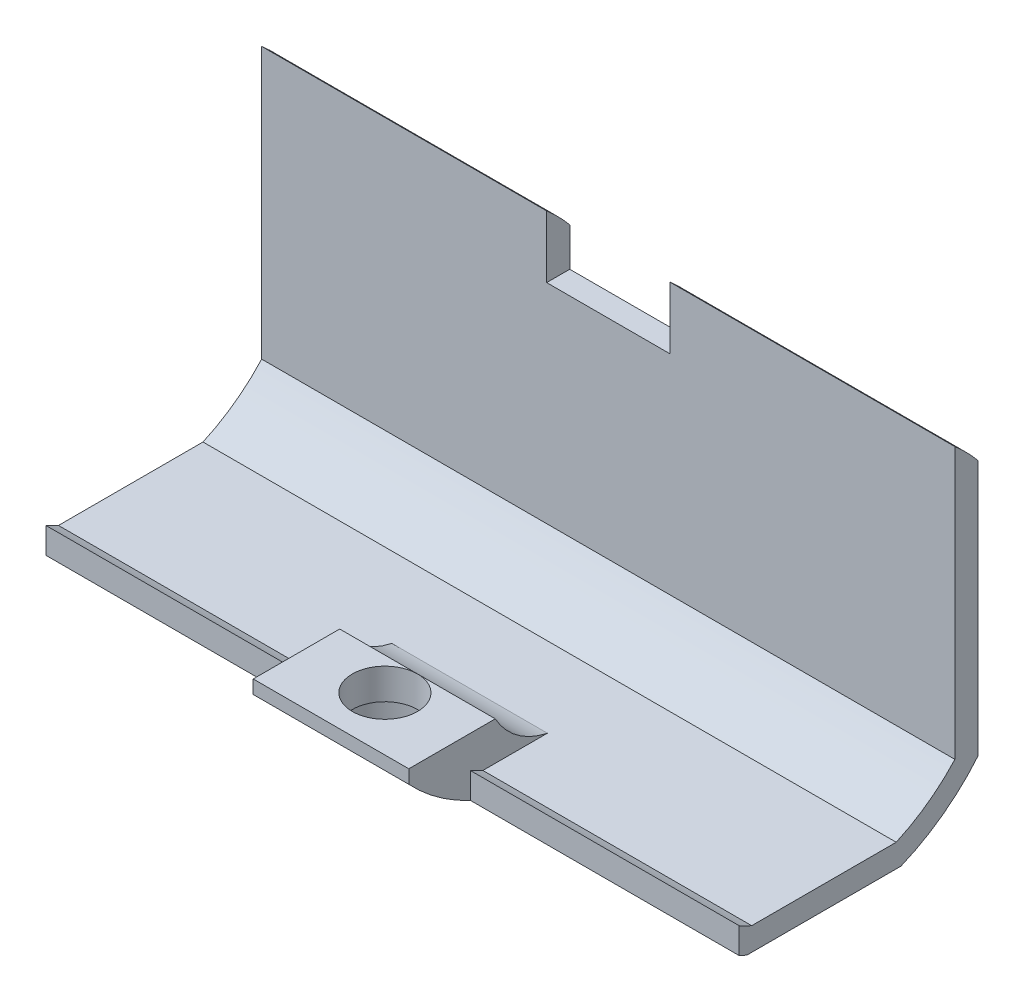
SolidWorks part; units mm, degrees
ref_plane "Plano frontal" through (0, 0, 0) normal (0, 0, 1) x (1, 0, 0)
ref_plane "Plano superior" through (0, 0, 0) normal (0, 1, 0) x (1, 0, 0)
ref_plane "Plano direito" through (0, 0, 0) normal (1, 0, 0) x (0, 0, -1)
sketch "Esboço2" plane through (0, 0, 0) normal (0, 0, 1) x (1, 0, 0)
  line L0 (0, 47.2571) -> (8.5, 47.2571)
  line L1 (0, 47.2571) -> (-8.5, 47.2571)
  line L2 (0, 23.9177) -> (8.5, 23.9177)
  line L3 (0, 23.9177) -> (-8.5, 23.9177)
  line L4 (0, 8.4) -> (0, 75) construction
  line L5 (0, 56.3545) -> (-16, 56.3545) construction
  line L6 (0, 56.3545) -> (16, 56.3545) construction
  line L7 (8.5, 47.2571) -> (8.5, 23.9177)
  line L8 (-8.5, 47.2571) -> (-8.5, 23.9177)
  line L20 (19.3117, 92) -> (-19.3117, 92)
  line L21 (-19.3117, 92) -> (-36.5, 70)
  line L22 (-36.5, 70) -> (-36.5, 0)
  line L23 (-36.5, 0) -> (-22.5, 0)
  line L24 (-22.5, 0) -> (-22.5, 8.4)
  line L25 (-22.5, 8.4) -> (22.5, 8.4)
  line L26 (22.5, 8.4) -> (22.5, 0)
  line L27 (22.5, 0) -> (36.5, 0)
  line L28 (36.5, 0) -> (36.5, 70)
  line L29 (36.5, 70) -> (19.3117, 92)
  circle A8 centre (29.2, 62) radius 2
  circle A9 centre (29.2, 49) radius 2
  circle A10 centre (29.2, 36) radius 2
  circle A11 centre (29.2, 23) radius 2
  circle A12 centre (-29.2, 23) radius 2
  circle A13 centre (0, 75) radius 2
  circle A14 centre (-7, 83.3) radius 2
  circle A15 centre (7, 83.3) radius 2
  circle A16 centre (-29.2, 36) radius 2
  circle A17 centre (-29.2, 49) radius 2
  circle A18 centre (-29.2, 62) radius 2
  circle A20 centre (-29.2, 10) radius 2
  circle A21 centre (29.2, 10) radius 2
  circle A26 centre (-16, 56.3545) radius 2.0867
  circle A27 centre (16, 56.3545) radius 2.0867
  point P31 (0, 23.9177)
  point P33 (0, 47.2571)
sketch "Model" plane through (0, 0, 0) normal (0, 0, 1) x (1, 0, 0)
  line L0 (-13.5, 51.7) -> (0, 51.7) construction
  line L1 (-22.5, 41.7) -> (0, 41.7) construction
  line L2 (0, 50.7729) -> (-23, 50.7729) construction
  line L3 (-22.5, 61.7) -> (-22.5, 41.7) construction
  line L4 (-22.5, 61.7) -> (0, 61.7) construction
  line L5 (-22.5, 61.7) -> (-21, 61.7) construction
  line L6 (-21, 61.7) -> (-21, 43.2) construction
  line L7 (0, 61.7) -> (0, 41.7) construction
  line L8 (0, 61.7) -> (0, 59.2) construction
  line L9 (0, 44.2) -> (0, 59.2)
  line L10 (-23, 63.7) -> (-23, 39.7)
  line L11 (-5.2, 59.2) -> (-0.8, 59.2) construction
  line L12 (-23, 63.7) -> (-5.55, 63.7)
  line L13 (0, 41.7) -> (0, 42.7) construction
  line L14 (-5.55, 63.7) -> (-5.55, 59.2)
  line L15 (0, 42.7) -> (-3.75, 42.7) construction
  line L16 (-3, 57) -> (-3, 61.4) construction
  line L17 (0, 59.2) -> (-5.55, 59.2)
  line L18 (-3, 61.4) -> (0, 61.4) construction
  line L19 (-3, 57) -> (0, 57) construction
  line L20 (-3.75, 41.7) -> (-3.75, 43.7) construction
  line L21 (0, 51.7) -> (-23, 51.7) construction
  line L22 (-3.75, 43.7) -> (0, 43.7) construction
  line L23 (-23, 39.7) -> (-5.55, 39.7)
  line L24 (-3.75, 41.7) -> (-3.75, 34.7) construction
  line L25 (-3.75, 34.7) -> (0, 34.7) construction
  line L26 (-5.55, 39.7) -> (-5.55, 44.2)
  line L27 (0, 44.2) -> (-5.55, 44.2)
  line L34 (-9.5, 39.7) -> (-17.5, 39.7) construction
  line L35 (-17.5, 39.7) -> (-25.5, 47.7) construction
  line L36 (-25.5, 47.7) -> (-25.5, 55.7) construction
  line L37 (-25.5, 55.7) -> (-17.5, 63.7) construction
  line L38 (-17.5, 63.7) -> (-9.5, 63.7) construction
  line L39 (-9.5, 63.7) -> (-5.55, 59.2) construction
  line L40 (-3, 46.75) -> (0, 46.75) construction
  line L41 (-3, 56.65) -> (0, 56.65) construction
  line L42 (-5.55, 44.2) -> (-5.55, 41.2) construction
  line L44 (-2.5, 36.75) -> (-5.55, 41.2) construction
  line L45 (-2.5, 36.75) -> (-2.5, 31.7) construction
  line L48 (-9.5, 31.7) -> (-9.5, 39.7) construction
  line L50 (-2.5, 31.7) -> (-2.5, 29.7) construction
  line L51 (-2.5, 29.7) -> (-9.5, 29.7) construction
  line L52 (-9.5, 29.7) -> (-9.5, 31.7) construction
  line L56 (-36.5, 50.7729) -> (-23.5, 50.7729) construction
  line L57 (-36.5, 70) -> (-36.5, 0) construction
  line L58 (0, 8.4) -> (0, 75) construction
  circle A0 centre (-13.5, 51.7) radius 8.35
  circle A2 centre (-21, 43.2) radius 1 construction
  circle A4 centre (-3, 59.2) radius 2.2 construction
  circle A7 centre (-13.5, 51.7) radius 8 construction
  arc A10 (-5.55, 59.2) -> (-3, 56.65) centre (-3, 59.2) ccw construction
  arc A11 (-3, 46.75) -> (-5.55, 44.2) centre (-3, 44.2) ccw construction
extrude "Ressalto-extrusão2" add sketch "Model" along normal blind 4
sketch "Esboço5" plane through (0, 0, 0) normal (0, 0, -1) x (-1, 0, 0)
  line L1 (23, 63.7) -> (25, 63.7)
  line L2 (23, 63.7) -> (23, 39.7)
  line L3 (23, 39.7) -> (25, 39.7)
  line L4 (25, 63.7) -> (25, 39.7)
extrude "Ressalto-extrusão3" add sketch "Esboço5" against normal blind 20
sketch "Esboço6" plane through (-25, 0, 0) normal (-1, 0, 0) x (0, 0, 1)
  line L0 (0, 51.7) -> (20, 51.7) construction
  line L1 (0, 39.7) -> (0, 63.7) construction
  line L2 (20, 39.7) -> (20, 63.7) construction
  line L3 (20, 51.7) -> (10, 63.7) construction
  line L4 (20, 63.7) -> (0, 63.7) construction
  line L5 (10, 63.7) -> (10, 39.7) construction
  line L6 (20, 39.7) -> (0, 39.7) construction
  circle A0 centre (10, 51.7) radius 13
extrude "Corte-extrusão1" cut sketch "Esboço6" against normal through all flip side to cut
sketch "Esboço8" plane through (-25, 0, 0) normal (-1, 0, 0) x (0, 0, 1)
  line L0 (10, 63.7) -> (10, 39.7) construction
  line L1 (15, 63.7) -> (5, 63.7) construction
  line L2 (15, 39.7) -> (5, 39.7) construction
  line L3 (10, 39.7) -> (0, 51.7) construction
  line L4 (0, 43.3934) -> (0, 60.0066) construction
  line L5 (0, 51.7) -> (20, 51.7) construction
  line L6 (20, 43.3934) -> (20, 60.0066) construction
  line L7 (10, 51.7) -> (7.885, 51.7) construction
  line L8 (10, 51.7) -> (8.5045, 53.1955) construction
  line L9 (10, 51.7) -> (10, 53.815) construction
  line L10 (10, 51.7) -> (11.4955, 53.1955) construction
  line L11 (10, 51.7) -> (12.115, 51.7) construction
  line L12 (10, 51.7) -> (11.4955, 50.2045) construction
  line L13 (10, 51.7) -> (10, 49.585) construction
  line L14 (10, 51.7) -> (8.5045, 50.2045) construction
  line L15 (7.885, 51.7) -> (10, 49.585)
  line L16 (10, 49.585) -> (12.115, 51.7)
  line L17 (12.115, 51.7) -> (10, 53.815)
  line L18 (10, 53.815) -> (7.885, 51.7)
  circle A0 centre (10, 51.7) radius 2.115 construction
  point P24 (10, 51.7)
  dimension "D1" = 8
extrude "Corte-extrusão2" cut sketch "Esboço8" against normal through all
mirror "Espelhar1" about plane through (0, 44.2, 4) normal (-1, 0, 0) of bodies 105
sketch "Esboço9" plane through (0, 0, 4) normal (0, 0, 1) x (1, 0, 0)
  line L0 (0, 59.2) -> (4, 59.2)
  line L1 (5.55, 59.2) -> (-5.55, 59.2) construction
  line L2 (4, 59.2) -> (4, 44.2)
  line L3 (-5.55, 44.2) -> (5.55, 44.2) construction
  line L4 (4, 44.2) -> (-4, 44.2)
  line L5 (-4, 44.2) -> (-4, 59.2)
  line L6 (-4, 59.2) -> (0, 59.2)
extrude "Ressalto-extrusão4" add sketch "Esboço9" along normal blind 4
sketch "Esboço10" plane through (0, 59.2, 0) normal (0, 1, 0) x (1, 0, 0)
  line L0 (0, 0) -> (0, -8) construction
  line L1 (4, -8) -> (-4, -8) construction
  line L2 (0, -4) -> (2.115, -4) construction
  line L3 (0, -4) -> (1.4955, -5.4955) construction
  line L4 (0, -4) -> (0, -6.115) construction
  line L5 (0, -4) -> (-1.4955, -5.4955) construction
  line L6 (0, -4) -> (-2.115, -4) construction
  line L7 (0, -4) -> (-1.4955, -2.5045) construction
  line L8 (0, -4) -> (0, -1.885) construction
  line L9 (0, -4) -> (1.4955, -2.5045) construction
  line L10 (0, -1.885) -> (-2.115, -4)
  line L11 (-2.115, -4) -> (0, -6.115)
  line L12 (0, -6.115) -> (2.115, -4)
  line L13 (2.115, -4) -> (0, -1.885)
  point P17 (0, -4)
  dimension "D1" = 8
extrude "Corte-extrusão3" cut sketch "Esboço10" against normal through all
sketch "Esboço13" plane through (23, 0, 0) normal (-1, 0, 0) x (0, 0, 1)
  line L0 (18.5, 43.954) -> (18.5, 59.446)
  line L1 (14.6904, 62.2) -> (5.3096, 62.2)
  line L2 (18.5, 43.954) -> (18.5, 41.8638)
  line L3 (4.5, 63.4792) -> (4.5, 61.7995)
  line L4 (15, 63.7) -> (5, 63.7)
  line L5 (4, 63.2326) -> (4, 40.1674)
  line L6 (5, 39.7) -> (15, 39.7)
  line L7 (20, 43.3934) -> (20, 60.0066)
  line L8 (15, 63.7) -> (5, 63.7)
  line L11 (20, 43.3934) -> (20, 60.0066)
  arc A0 (15, 39.7) -> (20, 43.3934) centre (10, 51.7) ccw construction
  arc A1 (18.5, 59.446) -> (14.6904, 62.2) centre (10, 51.7) ccw
  arc A2 (5.3096, 62.2) -> (4.5, 61.7995) centre (10, 51.7) ccw
  arc A3 (5.3096, 62.2) -> (4.6923, 61.9019) centre (10, 51.7) ccw construction
  arc A4 (5, 63.7) -> (4, 63.2326) centre (10, 51.7) ccw
  arc A5 (4, 40.1674) -> (5, 39.7) centre (10, 51.7) ccw
  arc A6 (15, 39.7) -> (20, 43.3934) centre (10, 51.7) ccw
  arc A7 (20, 60.0066) -> (15, 63.7) centre (10, 51.7) ccw
  arc A8 (5, 63.7) -> (4.5, 63.4792) centre (10, 51.7) ccw
  arc A9 (5, 63.7) -> (4, 63.2326) centre (10, 51.7) ccw construction
  arc A10 (18.5, 41.8638) -> (20, 43.3934) centre (10, 51.7) ccw
  arc A11 (20, 60.0066) -> (15, 63.7) centre (10, 51.7) ccw
  arc A12 (14.4231, 41.0846) -> (18.5, 43.954) centre (10, 51.7) ccw construction
  dimension "D1" = 0
  dimension "D2" = 1.5
extrude "Ressalto-extrusão5" add sketch "Esboço13" along normal blind 45 from offset 0.5
sketch "Esboço14" plane through (0, 59.2, 0) normal (0, 1, 0) x (1, 0, 0)
  line L0 (5.05, -4) -> (5.05, -8)
  line L1 (0, -6.115) -> (2.115, -4) construction
  line L2 (1.0575, -5.0575) -> (-1.1584, -2.8416) construction
  line L3 (-1.1584, -2.8416) -> (1.0575, -2.9425) construction
  line L4 (2.115, -4) -> (0, -1.885) construction
  line L5 (1.0575, -2.9425) -> (-1.0575, -5.0575) construction
  line L6 (-2.115, -4) -> (0, -6.115) construction
  line L7 (5.05, -8) -> (4, -8) construction
  line L8 (5.55, 0) -> (-5.55, 0)
  line L9 (-5.55, 0) -> (-5.55, -4)
  line L10 (-5.55, -4) -> (-4, -4)
  line L11 (-4, -4) -> (-4, -8)
  line L12 (-4, -8) -> (4, -8)
  line L13 (4, -8) -> (4, -4)
  line L14 (4, -4) -> (5.55, -4)
  line L15 (5.55, -4) -> (5.55, 0)
  line L16 (-5.05, -4) -> (-5.05, -8)
  line L17 (-5.05, -8) -> (-4, -8) construction
  line L18 (-5.05, -8) -> (-5.05, -9.5)
  line L19 (-5.05, -9.5) -> (5.05, -9.5)
  line L20 (-4, -8) -> (4, -8) construction
  line L21 (5.05, -9.5) -> (5.05, -8)
  line L24 (5.05, -4) -> (5.05, -0.5)
  line L26 (5.05, -0.5) -> (-5.05, -0.5)
  line L27 (-5.05, -0.5) -> (-5.05, -4)
  circle A0 centre (0, -4) radius 2.115
  dimension "D1" = 0
extrude "Ressalto-extrusão6" add sketch "Esboço14" along normal up to vertex (4.2792 mm away) from offset 0.5 up to point (-22.5, 63.4792, 4.5)
sketch "Esboço15" plane through (5.05, 0, 0) normal (1, 0, 0) x (0, 0, -1)
  line L0 (-5.5617, 63.9189) -> (-4.5, 63.9189)
  line L1 (-4.5, 63.9189) -> (-4.5, 64.9791)
  line L2 (-4.5, 64.9791) -> (0, 64.9791)
  line L3 (0, 64.9791) -> (0, 60.0066)
  arc A0 (0, 60.0066) -> (-4, 63.2326) centre (-10, 51.7) ccw construction
  arc A1 (0, 60.0066) -> (-5.5617, 63.9189) centre (-10, 51.7) ccw
extrude "Corte-extrusão4" cut sketch "Esboço15" against normal up to surface (10.1 mm away) up to face at (-5.05, 61.7951, 4.9008)
sketch "Esboço17" plane through (0, 63.7, 0) normal (0, 1, 0) x (1, 0, 0)
  circle A0 centre (0, -4) radius 3.5
sketch "Esboço18" plane through (0, 0, 20) normal (0, 0, 1) x (1, 0, 0)
  line L0 (-4, 45.8934) -> (0, 45.8934)
  line L2 (0, 45.8934) -> (4, 45.8934)
  line L3 (4, 45.8934) -> (4, 37.8132)
  line L4 (4, 37.8132) -> (-4, 37.8132)
  line L5 (-4, 37.8132) -> (-4, 45.8934)
extrude "Corte-extrusão7" cut sketch "Esboço18" against normal blind 10
extrude "Corte-extrusão8" cut sketch "Esboço17" against normal blind 2
sketch "Esboço21" plane through (5.05, 0, 0) normal (1, 0, 0) x (0, 0, -1)
  line L0 (-9.5, 59.7) -> (8, 59.7) construction
  line L1 (-9.5, 59.7) -> (-0.5, 59.7) construction
  line L2 (-6.115, 59.7) -> (-1.885, 59.7) construction
  line L3 (-6.115, 59.7) -> (-1.885, 59.7) construction
  line L4 (-6.115, 59.7) -> (-9.5, 59.7)
  line L5 (-9.5, 59.7) -> (-9.5, 62.2)
  arc A0 (-9.5, 62.2) -> (-6.115, 59.7) centre (-10.5021, 57.3015) cw
extrude "Corte-extrusão11" cut sketch "Esboço21" against normal up to surface (10.1 mm away) up to face at (-5.05, 61.4075, 4.8809)
move or copy body "Corpo-Mover/Copiar1" bodies to move or copy 108 copy no translate (0, 0, -38.6991)
sketch "Esboço19" plane through (0, 63.7, 0) normal (0, 1, 0) x (1, 0, 0)
  line L1 (-34.2602, 14.0031) -> (32.7464, 14.0031)
  line L2 (-34.2602, 14.0031) -> (-34.2602, 42.2081)
  line L3 (-34.2602, 42.2081) -> (32.7464, 42.2081)
  line L4 (32.7464, 14.0031) -> (32.7464, 42.2081)
extrude "Corte-extrusão9" cut sketch "Esboço19" against normal through all
move or copy body "Corpo-Mover/Copiar2" bodies to move or copy 124 copy no rotation origin (0, 0, 0) rotation axis (1, 0, 0) rotation angle 180
